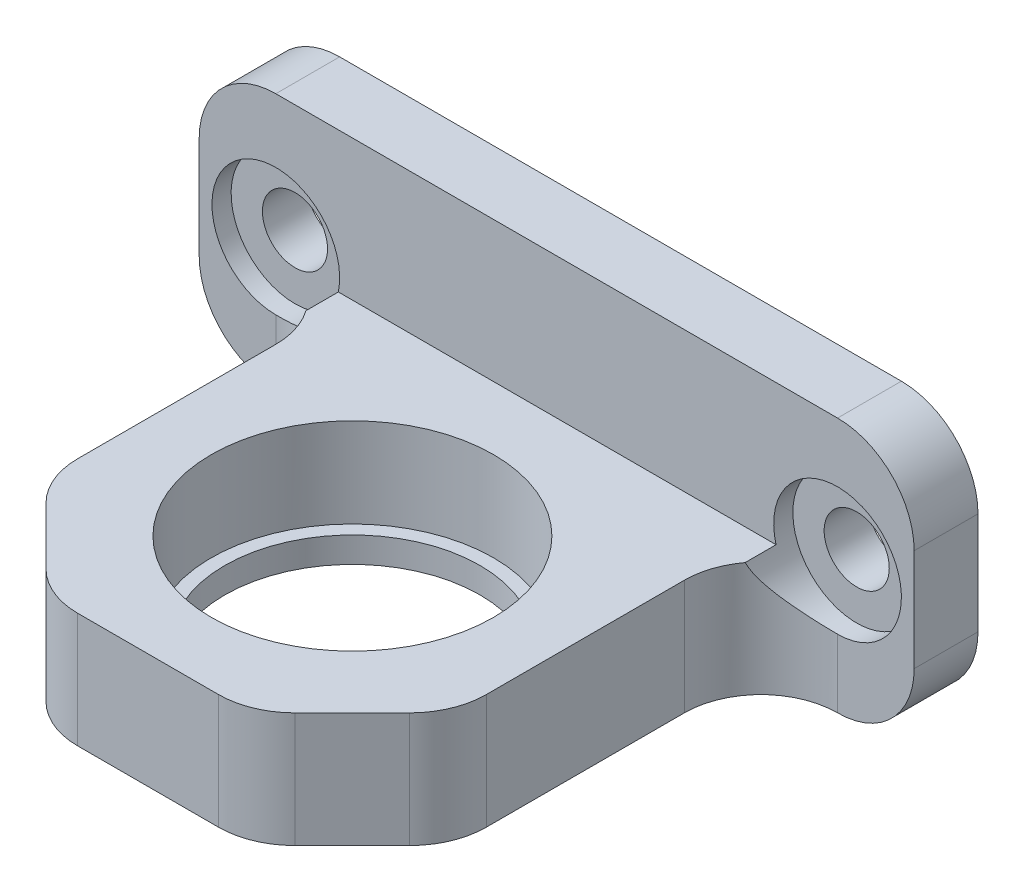
SolidWorks part; units mm, degrees
material "ABS"
ref_plane "Front Plane" through (0, 0, 0) normal (0, 0, 1) x (1, 0, 0)
ref_plane "Top Plane" through (0, 0, 0) normal (0, 1, 0) x (1, 0, 0)
ref_plane "Right Plane" through (0, 0, 0) normal (1, 0, 0) x (0, 0, -1)
sketch "Sketch2" plane through (0, 0, 0) normal (0, 1, 0) x (1, 0, 0)
  line L0 (-28, 21) -> (28, 21)
  line L5 (28, 21) -> (28, 16)
  line L6 (28, 16) -> (16, 16)
  line L7 (16, 16) -> (16, -16)
  line L8 (16, -16) -> (-16, -16)
  line L9 (-16, -16) -> (-16, 16)
  line L10 (-16, 16) -> (-28, 16)
  line L11 (-28, 16) -> (-28, 21)
  circle A0 centre (0, 0) radius 11.05
  dimension "D1" = 22.1
  dimension "D2" = 16
  dimension "D3" = 32
  dimension "D4" = 12
  dimension "D5" = 16
  dimension "D6" = 21
  dimension "D7" = 5
extrude "Boss-Extrude1" add sketch "Sketch2" along normal blind 9
chamfer "Chamfer1" distance 8 angle 45 2 edges at (16, 4.5, 16) (-16, 4.5, 16)
sketch "Sketch3" plane through (0, 0, 0) normal (0, -1, 0) x (1, 0, 0)
  circle A0 centre (0, 0) radius 10
  circle A1 centre (0, 0) radius 13
  dimension "D1" = 20
  dimension "D2" = 26
extrude "Boss-Extrude2" add sketch "Sketch3" against normal blind 2
sketch "Sketch5" plane through (0, 0, -16) normal (0, 0, 1) x (1, 0, 0)
  line L0 (28, 9) -> (28, 0) construction
  line L1 (-28, 9) -> (28, 9)
  line L2 (-28, 9) -> (-28, 20)
  line L3 (-28, 20) -> (28, 20)
  line L4 (28, 9) -> (28, 20)
  line L5 (-28, 0) -> (-16, 0) construction
  dimension "D1" = 20
extrude "Boss-Extrude3" add sketch "Sketch5" against normal up to surface (5 mm away) up to face at (0, 4.5, -21)
sketch "Sketch6" plane through (0, 0, -16) normal (0, 0, 1) x (1, 0, 0)
  line L2 (-28, 20) -> (-28, 0) construction
  line L3 (28, 20) -> (-28, 20) construction
  circle A0 centre (-22, 10) radius 2.55
  circle A1 centre (22, 10.3405) radius 2.55
  point P6 (-28, 10)
  point P9 (0, 20)
  dimension "D1" = 0
  dimension "D2" = 5.1
  dimension "D4" = 22
  dimension "D3" = 22
extrude "Cut-Extrude5" cut sketch "Sketch6" against normal through all
sketch "Sketch7" plane through (0, 0, -16) normal (0, 0, 1) x (1, 0, 0)
  circle A0 centre (22, 10.3405) radius 5
  circle A1 centre (-22, 10) radius 5
  dimension "D1" = 10
extrude "Cut-Extrude6" cut sketch "Sketch7" against normal blind 1.5 and the other way blind 10
fillet "Fillet1" radius 6 10 edges at (16, 4.5, 8) (8, 4.5, 16) (-8, 4.5, 16) (-16, 4.5, 8) (-16, 4.5, -16) (16, 4.5, -16) (28, 0, -18.5) (28, 20, -18.5) (-28, 20, -18.5) (-28, 0, -18.5)
equation "\"D2@Sketch2\"=\"D3@Sketch2\"/2"
equation "\"D5@Sketch2\"=\"D2@Sketch2\""
